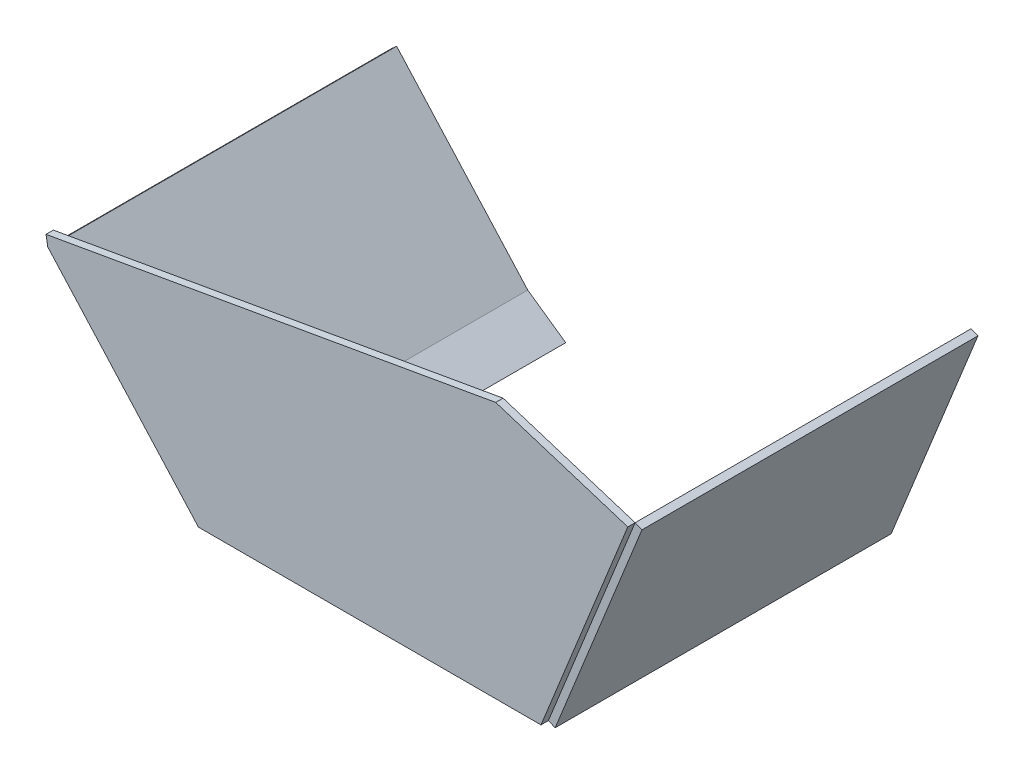
SolidWorks part; units mm, degrees
ref_plane "Front Plane" through (0, 0, 0) normal (0, 0, 1) x (1, 0, 0)
ref_plane "Top Plane" through (0, 0, 0) normal (0, 1, 0) x (1, 0, 0)
ref_plane "Right Plane" through (0, 0, 0) normal (1, 0, 0) x (0, 0, -1)
ref_axis "Axis1" through (0, 0, -14.8175) along (0, 0, 1)
sketch "Sketch1" plane through (0, 0, 0) normal (0, 0, 1) x (1, 0, 0)
  line L0 (-143.554, 0) -> (143.554, 0) construction
  line L1 (-164.2121, 22.9431) -> (-277.3802, 148.629)
  line L4 (-152.0988, 0) -> (-282.0991, 144.38)
  line L5 (-282.0991, 144.38) -> (-277.3802, 148.629)
  line L9 (-131.446, 0) -> (-164.2121, 22.9431)
  line L10 (-131.446, 0) -> (-152.0988, 0)
  line L11 (-164.2121, 22.9431) -> (-143.554, 0) construction
  line L12 (143.554, 0) -> (218.4753, 185.4368) construction
  line L13 (143.554, 0) -> (149.4416, -2.3788)
  line L14 (149.4416, -2.3788) -> (224.363, 183.058)
  line L15 (224.363, 183.058) -> (218.4753, 185.4368)
  line L16 (218.4753, 185.4368) -> (143.554, 0)
  point P4 (0, 0)
  dimension "D1" = 48
  dimension "D2" = 35
  dimension "D3" = 275
  dimension "D4" = 200
  dimension "D5" = 40
  dimension "D6" = 6.35
  dimension "D7" = 68
  dimension "D8" = 200
  dimension "D9" = 6.35
extrude "Boss-Extrude1" add sketch "Sketch1" along normal blind 290
sketch "Sketch2" plane through (0, 0, 290) normal (0, 0, 1) x (1, 0, 0)
  line L0 (-152.0988, 0) -> (-282.0991, 144.38)
  line L1 (-283.632, 153.0733) -> (104.4957, 221.5107)
  line L3 (143.554, 0) -> (-152.0988, 0)
  line L4 (-282.0991, 144.38) -> (-152.0988, 0) construction
  line L5 (143.554, 0) -> (218.4753, 185.4368)
  line L7 (-282.0991, 144.38) -> (-283.632, 153.0733)
  line L8 (-277.3802, 148.629) -> (-282.0991, 144.38) construction
  line L9 (218.4753, 185.4368) -> (104.4957, 221.5107)
  line L10 (143.554, 0) -> (104.4957, 221.5107) construction
  line L11 (-152.0988, 0) -> (-131.446, 0) construction
  dimension "D1" = 10
  dimension "D2" = 200
  dimension "D3" = 275
extrude "Boss-Extrude2" add sketch "Sketch2" along normal blind 6.35 separate body
ref_plane "Plane1" through (0, 0, 0) normal (0.9848, 0.1736, 0) x (0, 0, 1)
